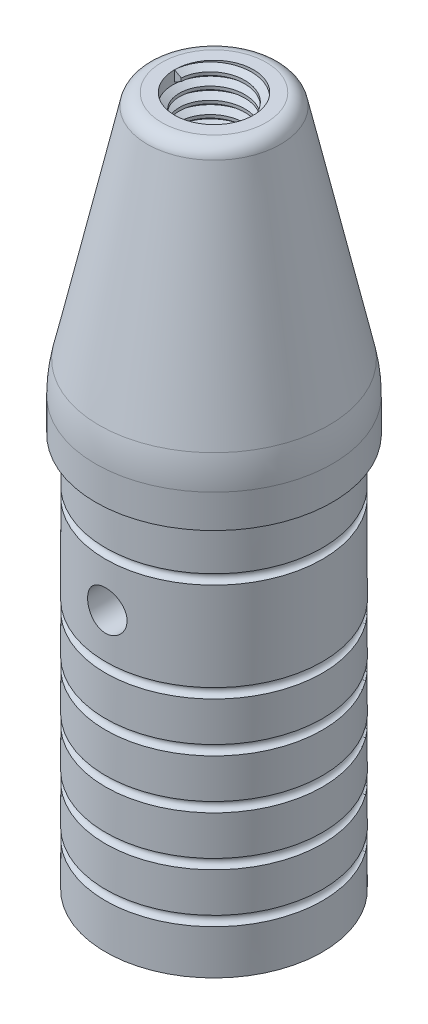
SolidWorks part; units mm, degrees
ref_plane "Ön Düzlem" through (0, 0, 0) normal (0, 0, 1) x (1, 0, 0)
ref_plane "Üst Düzlem" through (0, 0, 0) normal (0, 1, 0) x (1, 0, 0)
ref_plane "Sağ Düzlem" through (0, 0, 0) normal (1, 0, 0) x (0, 0, -1)
sketch "Çizim1" plane through (0, 0, 0) normal (0, 0, 1) x (1, 0, 0)
  line L21 (0, 0) -> (0, 70) construction
  line L22 (12, 40) -> (11, 40)
  line L23 (11, 40) -> (11, 0)
  line L24 (11, 0) -> (8, 0)
  line L25 (8, 0) -> (8, 40)
  line L26 (8, 40) -> (0, 40)
  line L27 (12, 40) -> (12, 45)
  line L28 (12, 45) -> (6.5, 70)
  line L29 (6.5, 70) -> (0, 70)
  line L30 (0, 70) -> (0, 40)
  dimension "D7" = 3
  dimension "D8" = 1
  dimension "D9" = 40
  dimension "D10" = 12
  dimension "D11" = 30
  dimension "D12" = 5
  dimension "D13" = 6.5
revolve "Döndür1" add sketch "Çizim1" angle 360 about L21
sketch "Çizim2" plane through (0, 70, 0) normal (0, 1, 0) x (1, 0, 0)
  circle A0 centre (0, 0) radius 4
  dimension "D1" = 8
extrude "Kes-Ekstrüzyon1" cut sketch "Çizim2" against normal blind 94
fillet "Radyus1" radius 15 1 edges at (0, 45, -12)
fillet "Radyus2" radius 1.5 1 edges at (0, 70, -6.5)
sketch "Sketch1" plane through (0, 0, 0) normal (0, 0, 1) x (1, 0, 0)
  line L0 (11, 0) -> (11, 40) construction
  line L1 (-12, 40) -> (12, 40) construction
  line L2 (11, 35) -> (-11, 35) construction
  line L3 (11, 25) -> (-11, 25) construction
  line L4 (11, 20) -> (-11, 20) construction
  line L5 (11, 15) -> (-11, 15) construction
  line L6 (11, 10) -> (-11, 10) construction
  line L7 (11, 5) -> (-11, 5) construction
  line L8 (0, 0) -> (0, 40) construction
  circle A0 centre (11, 35) radius 0.5
  circle A1 centre (11, 25) radius 0.5
  circle A2 centre (11, 20) radius 0.5
  circle A3 centre (11, 15) radius 0.5
  circle A4 centre (11, 10) radius 0.5
  circle A5 centre (11, 5) radius 0.5
  dimension "D6" = 1
  dimension "D7" = 1
  dimension "D8" = 1
  dimension "D9" = 1
  dimension "D10" = 1
  dimension "D11" = 1
  dimension "D1" = 5
  dimension "D2" = 10
  dimension "D3" = 10
  dimension "D4" = 5
  dimension "D5" = 5
revolve "Cut-Revolve1" cut sketch "Sketch1" angle 360 about L8
sketch "Sketch2" plane through (0, 0, 0) normal (0, 0, 1) x (1, 0, 0)
  line L0 (0, 40) -> (0, 30) construction
  line L1 (-11, 40) -> (11, 40) construction
  circle A0 centre (0, 30) radius 2
  dimension "D2" = 4
  dimension "D1" = 10
extrude "Cut-Extrude1" cut sketch "Sketch2" against normal blind 13 and the other way blind 13
thread "Thread1" pitch 1.25 method extrude profile "Thread Profile1" start angle 0, offset 0, length 0, pitch 1.25, diameter 8
ref_plane "Plane1" through (-4, 70, 0) normal (0, 0, 1) x (-1, 0, 0)
sketch "Thread Profile1" plane through (-4, 70, 0) normal (0, 0, 1) x (-1, 0, 0)
  line L0 (0, 0) -> (0, 1.25) construction
  line L11 (0, 0) -> (0, 1.0937)
  line L12 (0, 1.0937) -> (-0.6766, 0.7031)
  line L13 (-0.6766, 0.7031) -> (-0.6766, 0.3906)
  line L15 (-0.6766, 0.3906) -> (0, 0)
  line L17 (-0.6766, 0.5469) -> (0, 0.5469) construction
  point P2 (0, 0)
  dimension "Pitch" = 1.25
  dimension "Profile_Angle" = 60
  dimension "Profile_Land" = 0.3125
  dimension "Profile_Height" = 0.6766
